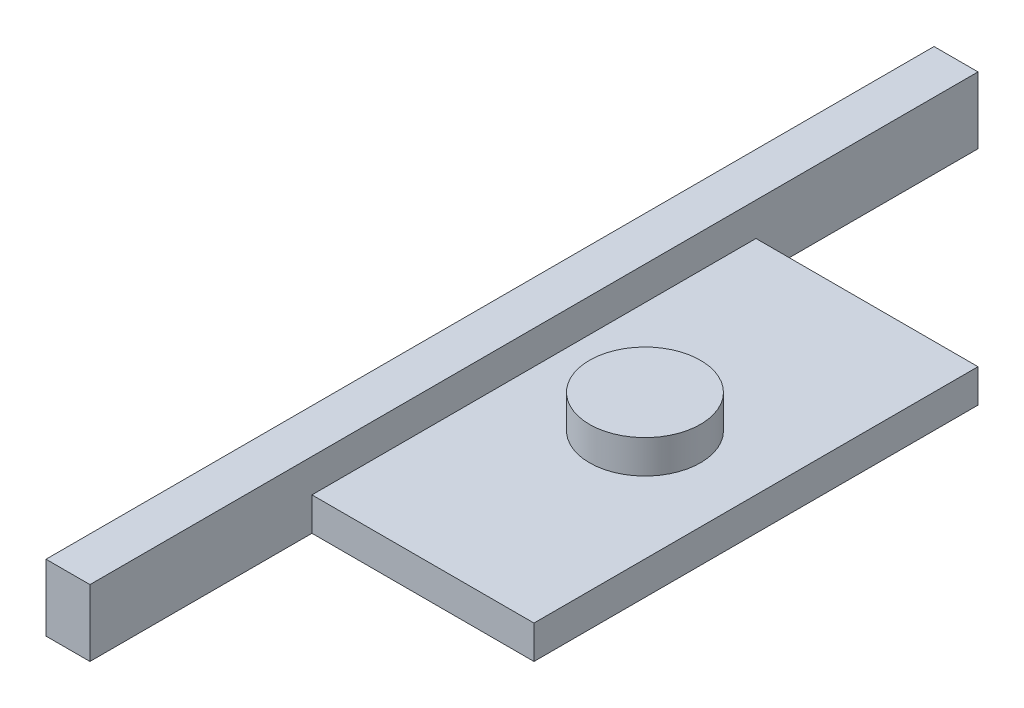
SolidWorks part; units mm, degrees
ref_plane "Alzado" through (0, 0, 0) normal (0, 0, 1) x (1, 0, 0)
ref_plane "Planta" through (0, 0, 0) normal (0, 1, 0) x (1, 0, 0)
ref_plane "Vista lateral" through (0, 0, 0) normal (1, 0, 0) x (0, 0, -1)
sketch "Croquis1" plane through (0, 0, 0) normal (0, 1, 0) x (1, 0, 0)
  line L1 (-65, -20) -> (65, -20)
  line L2 (-65, -20) -> (-65, 20)
  line L3 (-65, 20) -> (65, 20)
  line L4 (65, -20) -> (65, -10)
  line L5 (-65, -20) -> (65, 20) construction
  line L6 (-65, 20) -> (65, -20) construction
  line L10 (0, 0) -> (77.1384, 0) construction
  line L12 (10, 9.5) -> (40, 9.5)
  line L13 (10, 9.5) -> (10, 12.5)
  line L14 (10, 12.5) -> (40, 12.5)
  line L15 (40, 9.5) -> (40, 12.5)
  line L16 (10, 9.5) -> (40, 12.5) construction
  line L17 (10, 12.5) -> (40, 9.5) construction
  line L18 (10, -12.5) -> (40, -12.5)
  line L19 (10, -12.5) -> (10, -9.5)
  line L20 (10, -9.5) -> (40, -9.5)
  line L21 (40, -12.5) -> (40, -9.5)
  line L22 (10, -12.5) -> (40, -9.5) construction
  line L23 (10, -9.5) -> (40, -12.5) construction
  line L26 (65, 10) -> (65, 20)
  line L27 (65, 10) -> (75, 10)
  line L28 (75, 10) -> (75, -10)
  line L29 (75, -10) -> (65, -10)
  circle A2 centre (-50.1299, 0) radius 11
  circle A3 centre (-50.1299, 0) radius 12.5 construction
  circle A4 centre (-28.5951, 0) radius 2
  circle A5 centre (-13.5951, 0) radius 2
  circle A6 centre (50, 0) radius 2
  point P0 (0, 0)
  point P19 (25, 11)
  point P35 (25, -11)
  dimension "D8" = 22
  dimension "D12" = 25
  dimension "D13" = 4
  dimension "D14" = 4
  dimension "D17" = 4
  dimension "D1" = 130
  dimension "D2" = 20
  dimension "D3" = 10
  dimension "D6" = 40
  dimension "D9" = 3
  dimension "D10" = 30
  dimension "D11" = 40
  dimension "D15" = 15
  dimension "D16" = 10
  dimension "D18" = 12.5
  dimension "D19" = 12.5
extrude "Saliente-Extruir1" add sketch "Croquis1" along normal blind 3
sketch "Croquis2" plane through (0, 3, 0) normal (0, 1, 0) x (1, 0, 0)
  circle A0 centre (-50.1299, 0) radius 11
  circle A1 centre (-50.1299, 0) radius 13
  dimension "D1" = 2
extrude "Saliente-Extruir2" add sketch "Croquis2" along normal blind 4
sketch "Croquis3" plane through (0, 7, 0) normal (0, 1, 0) x (1, 0, 0)
  circle A0 centre (-50.1299, 0) radius 13
  circle A1 centre (-50.1299, 0) radius 9
  dimension "D1" = 18
extrude "Saliente-Extruir3" add sketch "Croquis3" along normal blind 2
chamfer "Chaflán1" distance 2 angle 45 1 edges at (-50.1299, 9, 13)
chamfer "Chaflán2" distance 10 angle 45 2 edges at (-65, 1.5, 20) (-65, 1.5, -20)
sketch "Croquis6" plane through (0, 3, 0) normal (0, 1, 0) x (1, 0, 0)
  line L0 (65, 0) -> (75, 0) construction
  line L1 (75, -10) -> (65, -10)
  line L2 (75, -10) -> (75, 10)
  line L3 (75, 10) -> (65, 10)
  line L4 (65, -10) -> (65, 10)
  circle A0 centre (70, 0) radius 2.5
  dimension "D1" = 5
extrude "Cortar-Extruir2" cut sketch "Croquis6" against normal blind 1.5
sketch "Croquis7" plane through (0, 3, 0) normal (0, 1, 0) x (1, 0, 0)
  line L0 (65, 20) -> (-55, 20) construction
  line L1 (63.0205, 20) -> (76.4991, 20)
  line L2 (63.0205, 20) -> (63.0205, -21.5963)
  line L3 (63.0205, -21.5963) -> (76.4991, -21.5963)
  line L4 (76.4991, 20) -> (76.4991, -21.5963)
extrude "Cortar-Extruir3" cut sketch "Croquis7" against normal blind 10 and the other way blind 10 flip side to cut
